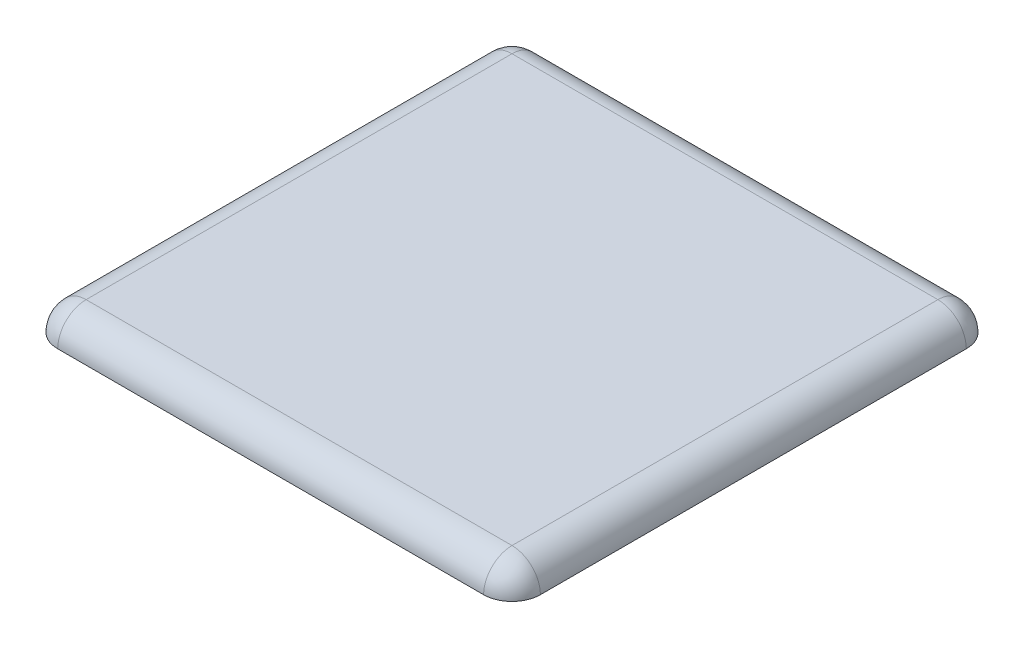
SolidWorks part; units mm, degrees
ref_plane "Front Plane" through (0, 0, 0) normal (0, 0, 1) x (1, 0, 0)
ref_plane "Top Plane" through (0, 0, 0) normal (0, 1, 0) x (1, 0, 0)
ref_plane "Right Plane" through (0, 0, 0) normal (1, 0, 0) x (0, 0, -1)
sketch "Sketch1" plane through (0, 0, 0) normal (0, 1, 0) x (1, 0, 0)
  line L1 (25.5, -25.5) -> (-25.5, -25.5)
  line L2 (25.5, -25.5) -> (25.5, 25.5)
  line L3 (25.5, 25.5) -> (-25.5, 25.5)
  line L4 (-25.5, -25.5) -> (-25.5, 25.5)
  line L5 (25.5, -25.5) -> (-25.5, 25.5) construction
  line L6 (25.5, 25.5) -> (-25.5, -25.5) construction
  point P0 (0, 0)
  dimension "D1" = 51
  dimension "D2" = 51
extrude "Boss-Extrude1" add sketch "Sketch1" along normal blind 3
fillet "Fillet1" radius 3 8 edges at (25.5, 1.5, -25.5) (25.5, 3, 0) (0, 3, -25.5) (-25.5, 1.5, -25.5) (-25.5, 3, 0) (0, 3, 25.5) (-25.5, 1.5, 25.5) (25.5, 1.5, 25.5)
